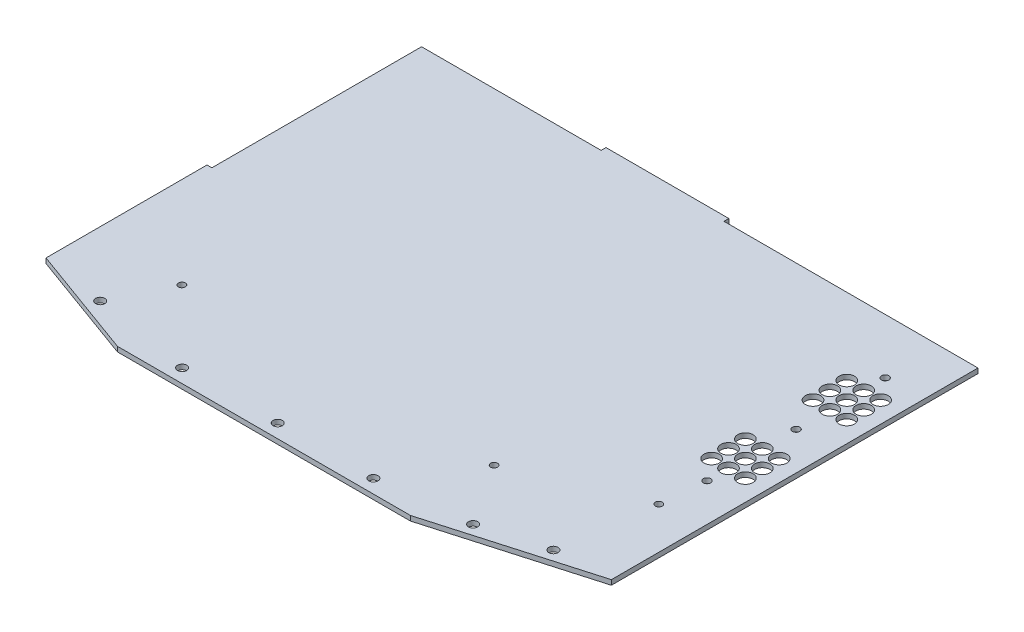
SolidWorks part; units mm, degrees
material "6061-T6 (SS)"
ref_plane "X-Y Datum" through (0, 0, 0) normal (0, 0, 1) x (1, 0, 0)
ref_plane "X-Z Datum" through (0, 0, 0) normal (0, 1, 0) x (1, 0, 0)
ref_plane "Y-Z Datum" through (0, 0, 0) normal (1, 0, 0) x (0, 0, -1)
sketch "Sketch1" plane through (0, 0, 0) normal (0, 0, 1) x (1, 0, 0)
  line L1 (-154.0556, -1.5875) -> (154.0556, -1.5875)
  line L2 (-154.0556, -1.5875) -> (-154.0556, 1.5875)
  line L3 (-154.0556, 1.5875) -> (154.0556, 1.5875)
  line L4 (154.0556, -1.5875) -> (154.0556, 1.5875)
  line L5 (-154.0556, -1.5875) -> (154.0556, 1.5875) construction
  line L6 (-154.0556, 1.5875) -> (154.0556, -1.5875) construction
  point P0 (0, 0)
  dimension "D1" = 3.175
  dimension "D2" = 308.1112
extrude "Boss-Extrude1" add sketch "Sketch1" along normal blind 267.83
sketch "Sketch3" plane through (154.0556, 0, 0) normal (1, 0, 0) x (0, 0, -1)
  line L9 (0, -1.5875) -> (0, 1.5875)
  line L10 (0, 1.5875) -> (-267.83, 1.5875)
  line L11 (-267.83, 1.5875) -> (-267.83, -1.5875)
  line L12 (-267.83, -1.5875) -> (0, -1.5875)
  line L13 (0, -1.5875) -> (0, 1.5875)
  line L14 (0, 1.5875) -> (-267.83, 1.5875)
  line L15 (-267.83, 1.5875) -> (-267.83, -1.5875)
  line L16 (-267.83, -1.5875) -> (0, -1.5875)
  dimension "D1" = 0
extrude "Boss-Extrude3" add sketch "Sketch3" along normal blind 3.175
sketch "Sketch4" plane through (0, 0, 267.83) normal (0, 0, 1) x (1, 0, 0)
  line L1 (157.2306, -1.5875) -> (208.1043, -1.5875)
  line L2 (157.2306, -1.5875) -> (157.2306, 1.5875)
  line L3 (157.2306, 1.5875) -> (208.1043, 1.5875)
  line L4 (208.1043, -1.5875) -> (208.1043, 1.5875)
  dimension "D1" = 3.175
  dimension "D2" = 50.8737
extrude "Boss-Extrude4" add sketch "Sketch4" against normal blind 267.83
sketch "Sketch6" plane through (0, 1.5875, 0) normal (0, 1, 0) x (1, 0, 0)
  line L0 (106.5043, -267.83) -> (106.5043, -223.38)
  line L1 (208.1043, -267.83) -> (-154.0556, -267.83) construction
  line L2 (208.1043, -223.38) -> (106.5043, -223.38)
  line L3 (208.1043, 0) -> (208.1043, -267.83) construction
  line L5 (106.5043, -267.83) -> (208.1047, -238.62)
  line L6 (208.1043, -223.38) -> (208.1047, -238.62)
  line M9 (-154.0556, -267.83) -> (208.1043, -267.83)
  line M10 (208.1043, -267.83) -> (208.1043, 0)
  dimension "D1" = 44.45
  dimension "D2" = 101.6
  dimension "D3" = 15.24
extrude "Cut-Extrude1" cut sketch "Sketch6" against normal through all contours L5 M9 M10 region at (174.2376, 1.5875, 258.0934)
sketch "Sketch11" plane through (0, -1.5875, 0) normal (0, -1, 0) x (1, 0, 0)
  line L0 (-84.2056, 267.83) -> (-84.2056, 242.43)
  line L1 (-154.0556, 267.83) -> (106.5043, 267.83) construction
  line L2 (-154.0556, 242.43) -> (-84.2056, 242.43)
  line L3 (-154.0556, 267.83) -> (-154.0556, 0) construction
  line L4 (-154.0556, 242.43) -> (-84.2056, 267.83)
  line M4 (-154.0556, 267.83) -> (-154.0556, 0)
  line M18 (106.5043, 267.83) -> (-154.0556, 267.83)
  dimension "D1" = 69.85
  dimension "D2" = 25.4
extrude "Cut-Extrude3" cut sketch "Sketch11" against normal through all contours L4 M4 M18 region at (-130.7723, -1.5875, 259.3633)
sketch "Sketch17" plane through (-154.0556, 0, 0) normal (-1, 0, 0) x (0, 0, 1)
  line L0 (136.4994, 1.5875) -> (136.4994, -1.5875)
  line L5 (242.43, 1.5875) -> (136.4994, 1.5875)
  line L9 (242.43, -1.5875) -> (0, -1.5875) construction
  line L10 (136.4994, -1.5875) -> (242.43, -1.5875)
  line L11 (242.43, -1.5875) -> (242.43, 1.5875)
extrude "Boss-Extrude5" add sketch "Sketch17" along normal blind 3.175
sketch "Sketch23" plane through (0, 1.5875, 0) normal (0, 1, 0) x (1, 0, 0)
  line L0 (-154.0556, -242.43) -> (-157.2306, -241.2755)
  line L1 (-157.2306, -242.43) -> (-157.2306, -136.4994) construction
  line L2 (-154.0556, -242.43) -> (-84.2056, -267.83) construction
  line L3 (-154.0556, -242.43) -> (-84.2056, -267.83) construction
extrude "Cut-Extrude7" cut sketch "Sketch23" against normal through all and the other way through all
sketch "Sketch25" plane through (0, -1.5875, 0) normal (0, -1, 0) x (1, 0, 0)
  line L0 (-157.2306, 241.2755) -> (-83.9957, 267.9063) construction
  line L1 (-50.9757, 267.83) -> (-50.9757, 258.94)
  line L2 (-157.2306, 241.2755) -> (-84.2056, 267.83) construction
  line L3 (-118.0827, 255.5111) -> (-115.3206, 247.9154)
  line L4 (-157.2306, 136.4994) -> (-157.2306, 241.2755) construction
  line L5 (-84.2056, 267.83) -> (106.5043, 267.83) construction
  line L6 (-50.9757, 258.94) -> (11.2543, 258.94) construction
  line L7 (11.2543, 258.94) -> (73.4843, 258.94) construction
  line L8 (172.5443, 248.8436) -> (172.5443, 240.7613)
  line L9 (106.5043, 267.83) -> (208.1043, 238.6201) construction
  line L10 (172.5443, 240.7613) -> (131.9043, 252.4453) construction
  circle A0 centre (-115.3206, 247.9154) radius 3
  circle A1 centre (-50.9757, 258.94) radius 3
  circle A2 centre (11.2543, 258.94) radius 3
  circle A3 centre (73.4843, 258.94) radius 3
  circle A4 centre (172.5443, 240.7613) radius 3
  circle A5 centre (131.9043, 252.4453) radius 3
  dimension "D2" = 90
  dimension "D3" = 6
  dimension "D13" = 8.89
  dimension "D1" = 8.0823
  dimension "D4" = 41.91
  dimension "D5" = 33.02
  dimension "D6" = 62.23
  dimension "D7" = 62.23
  dimension "D8" = 33.02
  dimension "D9" = 35.56
  dimension "D10" = 73.96
  dimension "D11" = 40.64
  dimension "D12" = 8.0823
extrude "Cut-Extrude8" cut sketch "Sketch25" against normal blind 3.175 contours A0 | A1 | A2 | A5 | A4 | A3 region at (-116.993, -1.5875, 245.5277) region at (-53.0371, -1.5875, 256.8787) region at (11.2543, -1.5875, 258.94) region at (170.4829, -1.5875, 238.7) region at (131.9043, -1.5875, 252.4453)
sketch "Sketch27" plane through (0, -1.5875, 0) normal (0, -1, 0) x (1, 0, 0)
  circle A0 centre (172.4867, 137.7748) radius 5 construction
  circle A1 centre (172.4867, 137.7748) radius 5
  circle A2 centre (183.4867, 137.7748) radius 5 construction
  circle A3 centre (183.4867, 137.7748) radius 5
  circle A4 centre (194.4867, 137.7748) radius 5 construction
  circle A5 centre (194.4867, 126.7748) radius 5 construction
  circle A6 centre (194.4867, 115.7748) radius 5 construction
  circle A7 centre (183.4867, 126.7748) radius 5 construction
  circle A8 centre (183.4867, 115.7748) radius 5 construction
  circle A9 centre (172.4867, 115.7748) radius 5 construction
  circle A10 centre (172.4867, 126.7748) radius 5 construction
  circle A11 centre (194.4867, 137.7748) radius 5
  circle A12 centre (194.4867, 126.7748) radius 5
  circle A13 centre (194.4867, 115.7748) radius 5
  circle A14 centre (183.4867, 126.7748) radius 5
  circle A15 centre (183.4867, 115.7748) radius 5
  circle A16 centre (172.4867, 115.7748) radius 5
  circle A17 centre (172.4867, 126.7748) radius 5
  circle A18 centre (194.4867, 71.7748) radius 5 construction
  circle A19 centre (194.4867, 60.7748) radius 5 construction
  circle A20 centre (194.4867, 49.7748) radius 5 construction
  circle A21 centre (183.4867, 71.7748) radius 5 construction
  circle A22 centre (183.4867, 60.7748) radius 5 construction
  circle A23 centre (183.4867, 49.7748) radius 5 construction
  circle A24 centre (172.4867, 49.7748) radius 5 construction
  circle A25 centre (172.4867, 60.7748) radius 5 construction
  circle A26 centre (172.4867, 71.7748) radius 5 construction
  circle A27 centre (194.4867, 71.7748) radius 5
  circle A28 centre (194.4867, 60.7748) radius 5
  circle A29 centre (194.4867, 49.7748) radius 5
  circle A30 centre (183.4867, 71.7748) radius 5
  circle A31 centre (183.4867, 60.7748) radius 5
  circle A32 centre (183.4867, 49.7748) radius 5
  circle A33 centre (172.4867, 49.7748) radius 5
  circle A34 centre (172.4867, 60.7748) radius 5
  circle A35 centre (172.4867, 71.7748) radius 5
extrude "Cut-Extrude9" cut sketch "Sketch27" against normal through all
sketch "Sketch28" plane through (0, -1.5875, 0) normal (0, -1, 0) x (1, 0, 0)
  point P0 (180.965, 180.586)
  point P1 (105.429, 212.285)
  point P3 (-97.7709, 212.285)
hole_wizard "M4 Clearance Hole1" positions "Sketch28" profile "Sketch29" hole size "M4" standard "ANSI Metric" end condition through all
sketch "Sketch29" plane through (180.965, -1.5875, 180.586) normal (1, 0, 0) x (0, 0, -1)
  line L0 (0, 0) -> (0, 3.175)
  line L1 (0, 3.175) -> (2.25, 3.175)
  line L2 (2.25, 3.175) -> (2.25, 0)
  line L5 (2.25, 0) -> (0, 0)
  line L11 (0, -6.35) -> (0, 107.95) construction
  dimension "Thru Hole Dia." = 4.5
  dimension "Thru Hole Depth" = 3.175
sketch "Sketch30" plane through (0, 0, 0) normal (0, 0, -1) x (-1, 0, 0)
  line L0 (37.216, 1.5875) -> (37.216, -1.5875) construction
  line L1 (-42.784, 1.5875) -> (37.216, 1.5875) construction
  line L2 (-42.784, 1.5875) -> (-42.784, -1.5875) construction
  line L3 (37.216, 1.5875) -> (37.216, -1.5875)
  line L4 (-42.784, 1.5875) -> (37.216, 1.5875)
  line L5 (-42.784, 1.5875) -> (-42.784, -1.5875)
  line L6 (154.0556, -1.5875) -> (-208.1043, -1.5875) construction
  line L7 (154.0556, -1.5875) -> (-208.1043, -1.5875)
  line M1 (154.0556, 1.5875) -> (-208.1043, 1.5875)
  line M3 (-208.1043, -1.5875) -> (154.0556, -1.5875)
extrude "Boss-Extrude6" add sketch "Sketch30" along normal blind 3.175 contours L5 L3 M1 M3 region at (2.784, 0, 0)
sketch "Sketch31" plane through (0, -1.5875, 0) normal (0, -1, 0) x (1, 0, 0)
  circle A0 centre (183.4867, 151.7748) radius 2.4 construction
  circle A1 centre (183.4867, 151.7748) radius 2.4
extrude "Cut-Extrude10" cut sketch "Sketch31" against normal through all both and the other way through all
pattern_linear "LPattern1" count 3 spacing 58 along (0, 0, -1) of "Cut-Extrude10"
